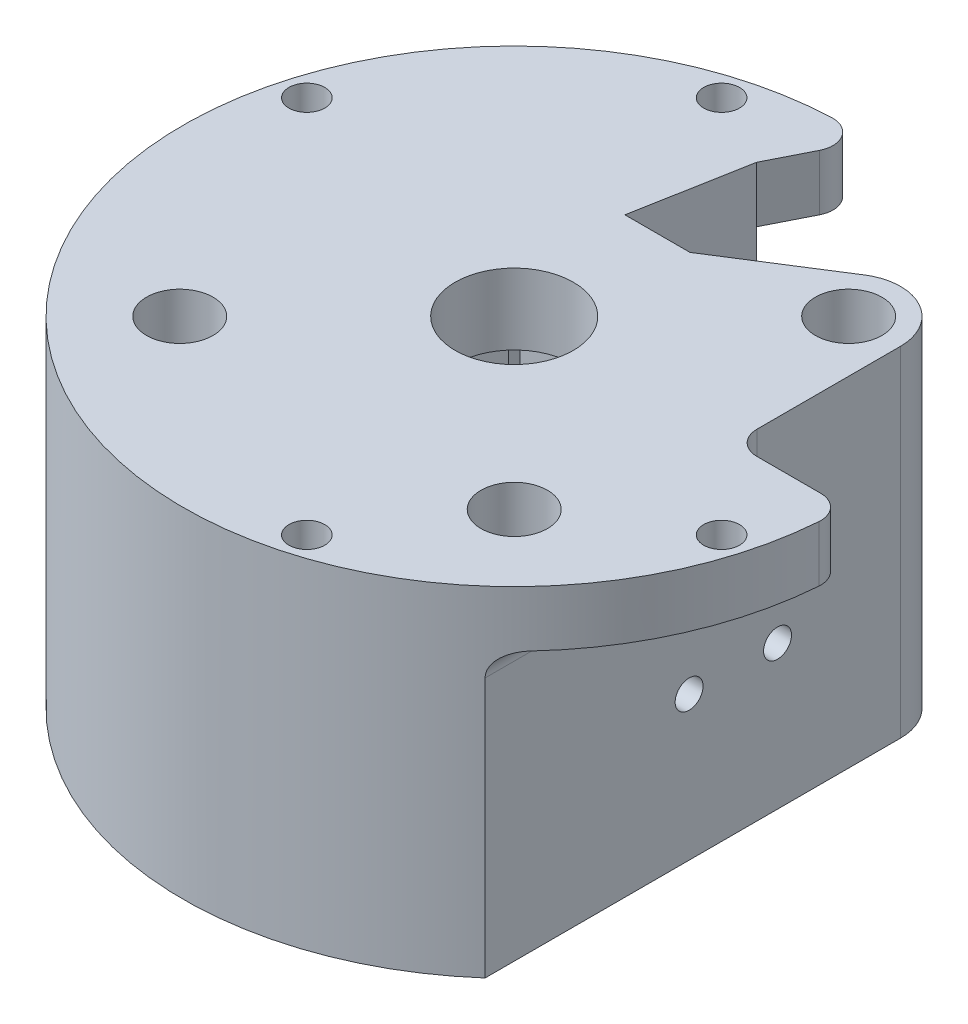
SolidWorks part; units mm, degrees
ref_plane "Front Plane" through (0, 0, 0) normal (0, 0, 1) x (1, 0, 0)
ref_plane "Top Plane" through (0, 0, 0) normal (0, 1, 0) x (1, 0, 0)
ref_plane "Right Plane" through (0, 0, 0) normal (1, 0, 0) x (0, 0, -1)
sketch "Sketch2" plane through (0, 0, 0) normal (0, 1, 0) x (1, 0, 0)
  line L0 (-46.3406, 15.0473) -> (-20.9548, -39.0545) construction
  line L1 (-17.9605, 17.9605) -> (-3.0236, 17.9605) construction
  line L2 (-17.9605, 17.9605) -> (-17.9605, -17.9605) construction
  line L3 (-17.9605, -17.9605) -> (17.9605, -17.9605) construction
  line L4 (17.9605, 17.9605) -> (17.9605, -17.9605) construction
  line L5 (-17.9605, 17.9605) -> (17.9605, -17.9605) construction
  line L6 (-17.9605, -17.9605) -> (17.9605, 17.9605) construction
  line L7 (10.05, -30.05) -> (-10.05, -30.05)
  line L8 (10.05, -30.05) -> (10.05, 10.05)
  line L9 (10.05, 10.05) -> (3.4925, 10.05)
  line L10 (-10.05, -30.05) -> (-10.05, 10.05)
  line L11 (10.05, -30.05) -> (-10.05, 10.05) construction
  line L12 (10.05, 10.05) -> (-10.05, -30.05) construction
  line L13 (-3.4925, 15.384) -> (3.4925, 15.384) construction
  line L14 (-3.4925, 15.384) -> (-3.4925, 10.05)
  line L15 (0, 10.05) -> (3.4925, 10.05) construction
  line L16 (3.4925, 15.384) -> (3.4925, 10.05)
  line L17 (0, 12.717) -> (3.4925, 10.05) construction
  line L18 (0, 12.717) -> (3.4925, 15.384) construction
  line L19 (-1.3182, 27.3309) -> (-10.8398, 32.142)
  line L20 (-1.3182, 27.3309) -> (-23.3118, -16.1961) construction
  line L21 (-23.3118, -16.1961) -> (-32.8333, -11.3851) construction
  line L22 (-10.8398, 32.142) -> (-32.8333, -11.3851) construction
  line L23 (-1.3182, 27.3309) -> (-32.8333, -11.3851) construction
  line L24 (-23.3118, -16.1961) -> (-10.8398, 32.142) construction
  line L25 (23.5324, -17.9605) -> (23.5324, -26.6597)
  line L26 (23.5324, -17.9605) -> (23.5324, 17.9605)
  line L27 (3.4925, 15.384) -> (14.9767, 22.6661)
  line L28 (-10.8398, 32.142) -> (-12.8493, 33.1573)
  line L29 (-3.4925, 15.384) -> (-1.3182, 27.3309)
  line L30 (-3.0236, 17.9605) -> (7.5558, 17.9605) construction
  line L31 (7.5558, 17.9605) -> (17.9605, 17.9605) construction
  line L32 (-3.4925, 15.384) -> (0, 12.717) construction
  line L33 (-3.4925, 10.05) -> (0, 12.717) construction
  line L34 (0, 10.05) -> (-3.4925, 10.05) construction
  line L35 (-3.4925, 10.05) -> (-10.05, 10.05)
  line L36 (-3.4925, 10.05) -> (0, 10.05) construction
  line L37 (3.4925, 10.05) -> (0, 10.05) construction
  arc A0 (-12.8493, 33.1573) -> (23.5324, -26.6597) centre (0, 0) ccw
  circle A1 centre (-17.9605, 17.9605) radius 3.5719 construction
  circle A2 centre (17.9605, 17.9605) radius 3.5719
  circle A3 centre (17.9605, -17.9605) radius 3.5719
  circle A4 centre (-17.9605, -17.9605) radius 3.5719
  arc A5 (-4.4901, 4.4901) -> (4.4901, 4.4901) centre (0, 0) ccw construction
  arc A6 (-7.1064, 7.1064) -> (7.1064, 7.1064) centre (0, 0) ccw construction
  circle A7 centre (-17.9605, -17.9605) radius 5.5719 construction
  arc A8 (23.5324, -17.9605) -> (17.9605, -12.3886) centre (17.9605, -17.9605) ccw construction
  arc A9 (23.5324, 17.9605) -> (14.9767, 22.6661) centre (17.9605, 17.9605) ccw
  arc A10 (23.5324, -26.6597) -> (-12.8493, 33.1573) centre (0, 0) ccw construction
  arc A11 (0, 10.05) -> (-7.1064, 7.1064) centre (0, 0) ccw construction
  arc A12 (4.4901, 4.4901) -> (-4.4901, 4.4901) centre (0, 0) ccw construction
  arc A13 (7.1064, 7.1064) -> (0, 10.05) centre (0, 0) ccw construction
  arc A14 (14.0206, 14.0206) -> (17.9605, 12.3886) centre (17.9605, 17.9605) ccw construction
  arc A15 (12.3886, 17.9605) -> (14.0206, 14.0206) centre (17.9605, 17.9605) ccw construction
  arc A16 (14.9767, 22.6661) -> (12.3886, 17.9605) centre (17.9605, 17.9605) ccw construction
  arc A17 (17.9605, 12.3886) -> (23.5324, 17.9605) centre (17.9605, 17.9605) ccw construction
  arc A18 (12.3886, -17.9605) -> (23.5324, -17.9605) centre (17.9605, -17.9605) ccw construction
  arc A19 (14.0206, -14.0206) -> (12.3886, -17.9605) centre (17.9605, -17.9605) ccw construction
  arc A20 (17.9605, -12.3886) -> (14.0206, -14.0206) centre (17.9605, -17.9605) ccw construction
  point P12 (0, -10)
  point P17 (0, 12.717)
  point P23 (-17.0758, 7.9729)
  point P35 (-32.1922, -15.1054)
  dimension "D1" = 71.12
  dimension "D3" = 7.1437
  dimension "D4" = 12.7
  dimension "D2" = 50.8
  dimension "D5" = 20.1
  dimension "D6" = 40.1
  dimension "D7" = 10
  dimension "D8" = 6.985
  dimension "D9" = 5.334
  dimension "D10" = 10.668
  dimension "D11" = 48.768
  dimension "D12" = 10.668
  dimension "D13" = 2
  dimension "D14" = 1
  dimension "D15" = 38.056
extrude "Boss-Extrude1" add sketch "Sketch2" along normal blind 1.905
sketch "Sketch3" plane through (0, 1.905, 0) normal (0, 1, 0) x (1, 0, 0)
  line L0 (-1.3182, 27.3309) -> (-23.3118, -16.1961) construction
  line L1 (-10.8398, 32.142) -> (-32.8333, -11.3851) construction
  line L2 (-23.3118, -16.1961) -> (-32.8333, -11.3851) construction
  line L3 (-10.8398, 32.142) -> (-32.8333, -11.3851)
  line L4 (-1.3182, 27.3309) -> (-9.7636, 10.6168)
  line L5 (-23.3118, -16.1961) -> (-32.8333, -11.3851)
  line L6 (-10.05, 10.05) -> (-9.415, 10.05) construction
  line L7 (-9.7636, 10.6168) -> (-10.05, 10.05) construction
  line L8 (-10.3364, 9.4832) -> (-23.3118, -16.1961)
  line L9 (-10.05, 10.05) -> (-10.3364, 9.4832) construction
  line L10 (-10.05, 9.415) -> (-10.05, 10.05) construction
  line L11 (-10.05, 10.05) -> (-3.4925, 10.05)
  line L12 (-3.4925, 10.05) -> (-3.4925, 15.384)
  line L13 (-3.4925, 15.384) -> (-1.3182, 27.3309)
  line L14 (-1.3182, 27.3309) -> (-12.8493, 33.1573)
  line L15 (23.5324, -26.6597) -> (23.5324, 17.9605)
  line L16 (14.9767, 22.6661) -> (3.4925, 15.384)
  line L17 (3.4925, 15.384) -> (3.4925, 10.05)
  line L18 (3.4925, 10.05) -> (10.05, 10.05)
  line L19 (10.05, 10.05) -> (10.05, -30.05)
  line L20 (10.05, -30.05) -> (-10.05, -30.05)
  line L21 (-10.05, -30.05) -> (-10.05, 10.05)
  line L22 (-9.415, 10.05) -> (-3.4925, 10.05)
  line L23 (-3.4925, 10.05) -> (-3.4925, 15.384)
  line L24 (-3.4925, 15.384) -> (-1.3182, 27.3309)
  line L25 (-10.8398, 32.142) -> (-12.8493, 33.1573)
  line L26 (23.5324, -26.6597) -> (23.5324, 17.9605)
  line L27 (14.9767, 22.6661) -> (3.4925, 15.384)
  line L28 (3.4925, 15.384) -> (3.4925, 10.05)
  line L29 (3.4925, 10.05) -> (10.05, 10.05)
  line L30 (10.05, 10.05) -> (10.05, -30.05)
  line L31 (10.05, -30.05) -> (-10.05, -30.05)
  line L32 (-10.05, -30.05) -> (-10.05, 9.415)
  line L33 (-1.3182, 27.3309) -> (-10.8398, 32.142) construction
  arc A0 (-10.3364, 9.4832) -> (-10.05, 9.415) centre (-10.05, 10.05) ccw
  circle A1 centre (17.9605, 17.9605) radius 3.5719 construction
  circle A2 centre (17.9605, -17.9605) radius 3.5719 construction
  arc A3 (-12.8493, 33.1573) -> (23.5324, -26.6597) centre (0, 0) ccw
  arc A4 (23.5324, 17.9605) -> (14.9767, 22.6661) centre (17.9605, 17.9605) ccw
  arc A5 (-12.8493, 33.1573) -> (23.5324, -26.6597) centre (0, 0) ccw
  arc A6 (23.5324, 17.9605) -> (14.9767, 22.6661) centre (17.9605, 17.9605) ccw
  circle A7 centre (-17.9605, -17.9605) radius 3.5719 construction
  circle A8 centre (17.9605, 17.9605) radius 3.5719
  circle A9 centre (17.9605, -17.9605) radius 3.5719
  circle A10 centre (-17.9605, -17.9605) radius 3.5719
  arc A11 (-9.7636, 10.6168) -> (-10.3364, 9.4832) centre (-10.05, 10.05) ccw construction
  arc A12 (-10.05, 9.415) -> (-9.415, 10.05) centre (-10.05, 10.05) ccw construction
  arc A13 (-9.415, 10.05) -> (-9.7636, 10.6168) centre (-10.05, 10.05) ccw
  dimension "D1" = 1.27
  dimension "D2" = 0
extrude "Boss-Extrude2" add sketch "Sketch3" along normal blind 19.558
sketch "Sketch4" plane through (0, 21.463, 0) normal (0, 1, 0) x (1, 0, 0)
  line L0 (0, 10.05) -> (3.4925, 10.05) construction
  line L1 (-3.4925, 15.384) -> (3.4925, 15.384) construction
  line L2 (0, 10.05) -> (-3.4925, 10.05) construction
  line L3 (0, 10.05) -> (-3.4925, 10.05)
  line L4 (0, 10.05) -> (3.4925, 10.05)
  line L5 (-3.4925, 15.384) -> (3.4925, 15.384)
  line L6 (-23.3118, -16.1961) -> (-32.8333, -11.3851) construction
  line L7 (-10.8398, 32.142) -> (-32.8333, -11.3851) construction
  line L8 (-1.3182, 27.3309) -> (-23.3118, -16.1961) construction
  line L9 (-23.3118, -16.1961) -> (-32.8333, -11.3851)
  line L10 (-10.8398, 32.142) -> (-32.8333, -11.3851)
  line L11 (-10.05, 10.05) -> (-3.4925, 10.05)
  line L12 (-10.05, -30.05) -> (-10.05, 10.05)
  line L13 (10.05, -30.05) -> (-10.05, -30.05)
  line L14 (10.05, 10.05) -> (10.05, -30.05)
  line L15 (3.4925, 10.05) -> (10.05, 10.05)
  line L16 (3.4925, 15.384) -> (3.4925, 10.05)
  line L17 (14.9767, 22.6661) -> (3.4925, 15.384)
  line L18 (23.5324, -26.6597) -> (23.5324, 17.9605)
  line L19 (-1.3182, 27.3309) -> (-12.8493, 33.1573)
  line L20 (-3.4925, 15.384) -> (-1.3182, 27.3309)
  line L21 (-3.4925, 10.05) -> (-3.4925, 15.384)
  line L22 (-9.415, 10.05) -> (-3.4925, 10.05)
  line L23 (-10.05, -30.05) -> (-10.05, 9.415)
  line L24 (10.05, -30.05) -> (-10.05, -30.05)
  line L25 (10.05, 10.05) -> (10.05, -30.05)
  line L26 (3.4925, 10.05) -> (10.05, 10.05)
  line L27 (3.4925, 15.384) -> (3.4925, 10.05) construction
  line L28 (14.9767, 22.6661) -> (3.4925, 15.384)
  line L29 (23.5324, -26.6597) -> (23.5324, 17.9605)
  line L30 (-10.8398, 32.142) -> (-12.8493, 33.1573)
  line L31 (-3.4925, 15.384) -> (-1.3182, 27.3309)
  line L32 (-3.4925, 10.05) -> (-3.4925, 15.384) construction
  line L33 (-1.3182, 27.3309) -> (-9.7636, 10.6168)
  line L34 (-1.3182, 27.3309) -> (-10.8398, 32.142) construction
  line L35 (-10.05, 10.05) -> (-10.3364, 9.4832) construction
  line L36 (-10.3364, 9.4832) -> (-23.3118, -16.1961)
  line L37 (-10.05, 9.415) -> (-10.05, 10.05) construction
  line L38 (-10.05, 10.05) -> (-9.415, 10.05) construction
  line L39 (-9.7636, 10.6168) -> (-10.05, 10.05) construction
  circle A0 centre (17.9605, 17.9605) radius 3.5719 construction
  circle A1 centre (17.9605, -17.9605) radius 3.5719 construction
  arc A2 (23.5324, 17.9605) -> (14.9767, 22.6661) centre (17.9605, 17.9605) ccw
  arc A3 (-12.8493, 33.1573) -> (23.5324, -26.6597) centre (0, 0) ccw
  arc A4 (23.5324, 17.9605) -> (14.9767, 22.6661) centre (17.9605, 17.9605) ccw
  arc A5 (-12.8493, 33.1573) -> (23.5324, -26.6597) centre (0, 0) ccw
  circle A6 centre (-17.9605, -17.9605) radius 3.5719 construction
  circle A7 centre (17.9605, 17.9605) radius 3.5719
  circle A8 centre (17.9605, -17.9605) radius 3.5719
  circle A9 centre (-17.9605, -17.9605) radius 3.5719
  arc A10 (-9.415, 10.05) -> (-9.7636, 10.6168) centre (-10.05, 10.05) ccw construction
  arc A11 (-10.3364, 9.4832) -> (-10.05, 9.415) centre (-10.05, 10.05) ccw construction
  arc A12 (-9.415, 10.05) -> (-9.7636, 10.6168) centre (-10.05, 10.05) ccw
  arc A13 (-10.3364, 9.4832) -> (-10.05, 9.415) centre (-10.05, 10.05) ccw
  dimension "D1" = 0
extrude "Boss-Extrude3" add sketch "Sketch4" along normal blind 7.366
sketch "Sketch5" plane through (0, 28.829, 0) normal (0, 1, 0) x (1, 0, 0)
  line L0 (3.4925, 15.384) -> (-3.4925, 15.384) construction
  line L1 (3.4925, 15.384) -> (-3.4925, 15.384)
  line L11 (-10.05, 10.05) -> (-3.4925, 10.05)
  line L12 (-10.05, -30.05) -> (-10.05, 10.05)
  line L13 (10.05, -30.05) -> (-10.05, -30.05)
  line L14 (10.05, 10.05) -> (10.05, -30.05)
  line L15 (3.4925, 10.05) -> (10.05, 10.05)
  line L16 (3.4925, 15.384) -> (3.4925, 10.05)
  line L17 (14.9767, 22.6661) -> (3.4925, 15.384)
  line L18 (23.5324, -26.6597) -> (23.5324, 17.9605)
  line L19 (-1.3182, 27.3309) -> (-12.8493, 33.1573)
  line L20 (-3.4925, 15.384) -> (-1.3182, 27.3309)
  line L21 (-3.4925, 10.05) -> (-3.4925, 15.384)
  line L22 (-10.05, 10.05) -> (-3.4925, 10.05) construction
  line L23 (-10.05, -30.05) -> (-10.05, 10.05) construction
  line L24 (10.05, -30.05) -> (-10.05, -30.05) construction
  line L25 (10.05, 10.05) -> (10.05, -30.05) construction
  line L26 (3.4925, 10.05) -> (10.05, 10.05) construction
  line L27 (3.4925, 15.384) -> (3.4925, 10.05) construction
  line L28 (14.9767, 22.6661) -> (3.4925, 15.384)
  line L29 (23.5324, -26.6597) -> (23.5324, 17.9605)
  line L30 (-1.3182, 27.3309) -> (-12.8493, 33.1573)
  line L31 (-3.4925, 15.384) -> (-1.3182, 27.3309)
  line L32 (-3.4925, 10.05) -> (-3.4925, 15.384) construction
  circle A0 centre (17.9605, 17.9605) radius 3.5719 construction
  circle A1 centre (17.9605, -17.9605) radius 3.5719 construction
  arc A2 (23.5324, 17.9605) -> (14.9767, 22.6661) centre (17.9605, 17.9605) ccw
  arc A3 (-12.8493, 33.1573) -> (23.5324, -26.6597) centre (0, 0) ccw
  arc A4 (23.5324, 17.9605) -> (14.9767, 22.6661) centre (17.9605, 17.9605) ccw
  arc A5 (-12.8493, 33.1573) -> (23.5324, -26.6597) centre (0, 0) ccw
  circle A6 centre (-17.9605, -17.9605) radius 3.5719 construction
  circle A7 centre (17.9605, 17.9605) radius 3.5719
  circle A8 centre (17.9605, -17.9605) radius 3.5719
  circle A9 centre (-17.9605, -17.9605) radius 3.5719
  arc A10 (4.4901, 4.4901) -> (-4.4901, 4.4901) centre (0, 0) ccw construction
  arc A11 (-4.4901, 4.4901) -> (4.4901, 4.4901) centre (0, 0) ccw construction
  arc A12 (4.4901, 4.4901) -> (-4.4901, 4.4901) centre (0, 0) ccw
  arc A13 (-4.4901, 4.4901) -> (4.4901, 4.4901) centre (0, 0) ccw
  dimension "D1" = 0
extrude "Boss-Extrude4" add sketch "Sketch5" along normal blind 7.62
sketch "Sketch8" plane through (0, 36.449, 0) normal (0, 1, 0) x (1, 0, 0)
  line L0 (-1.3182, 27.3309) -> (-12.8493, 33.1573)
  line L1 (-1.3182, 27.3309) -> (2.7846, 35.4508)
  line L2 (23.5324, 0) -> (35.56, 0)
  line L3 (23.5324, -17.9605) -> (23.5324, 17.9605) construction
  line L4 (23.5324, -17.9605) -> (23.5324, 0)
  line L5 (23.5324, -17.9605) -> (23.5324, -26.6597) construction
  line L6 (23.5324, -17.9605) -> (23.5324, -26.6597)
  arc A0 (23.5324, -26.6597) -> (-12.8493, 33.1573) centre (0, 0) ccw construction
  arc A1 (23.5324, -26.6597) -> (35.56, 0) centre (0, 0) ccw
  arc A2 (35.56, 0) -> (2.7846, 35.4508) centre (0, 0) ccw construction
  arc A3 (2.7846, 35.4508) -> (-12.8493, 33.1573) centre (0, 0) ccw
extrude "Boss-Extrude5" add sketch "Sketch8" against normal blind 6
sketch "Sketch7" plane through (0, 36.449, 0) normal (0, 1, 0) x (1, 0, 0)
  line L0 (-31.4663, 9.1924) -> (-9.1924, 31.4663) construction
  line L1 (-9.1924, 31.4663) -> (31.4663, -9.1924) construction
  line L2 (31.4663, -9.1924) -> (9.1924, -31.4663) construction
  line L3 (9.1924, -31.4663) -> (-31.4663, 9.1924) construction
  line L4 (-17.9605, -17.9605) -> (17.9605, 17.9605) construction
  line L5 (-31.4663, 9.1924) -> (31.4663, -9.1924) construction
  line L6 (9.1924, -31.4663) -> (-9.1924, 31.4663) construction
  circle A0 centre (-31.4663, 9.1924) radius 1.925
  circle A1 centre (-9.1924, 31.4663) radius 1.925
  circle A2 centre (31.4663, -9.1924) radius 1.925
  circle A3 centre (9.1924, -31.4663) radius 1.925
  point P6 (0, 0)
  dimension "D3" = 3.85
  dimension "D1" = 57.5
  dimension "D2" = 31.5
extrude "Cut-Extrude2" cut sketch "Sketch7" against normal blind 5.75
sketch "Sketch6" plane through (23.5324, 0, 0) normal (1, 0, 0) x (0, 0, -1)
  line L1 (-4.75, 15.449) -> (4.75, 15.449) construction
  line L5 (0, 30.449) -> (-26.6597, 30.449) construction
  line L6 (0, 30.449) -> (-26.6597, 30.449) construction
  circle A0 centre (-4.75, 15.449) radius 1.5
  circle A1 centre (4.75, 15.449) radius 1.5
  point P3 (0, 15.449)
  dimension "D3" = 15
  dimension "D1" = 3
  dimension "D2" = 9.5
fillet "Fillet1" radius 2.54 8 edges at (23.5324, 30.449, 13.3299) (0, 21.463, -10.05) (0, 21.463, -15.384) (2.7846, 33.449, -35.4508) (-12.8493, 15.2245, -33.1573) (3.4925, 0, -12.717) (35.56, 33.449, 0) (23.5324, 33.449, 0)
extrude "Cut-Extrude3" cut sketch "Sketch6" against normal blind 4
equation "\"AIRFRAME_OD\"= 3.091in"
equation "\"AIRFRAME_ID\"= 3.00in"
equation "\"FLAT_T\"= 0.125in"
equation "\"NOSE_EXP_L\"= 3.5in"
equation "\"NOSE_SHOULDER_L\"= 5in"
equation "\"MAIN_L\"= 30in"
equation "\"RECO_COUP_L\"= 6in"
equation "\"RECO_SWITCH_L\"= 1.5in"
equation "\"DROGUE_L\"= 14in"
equation "\"ATS_FORE_COUP_L\"= 4in"
equation "\"ATS_AFT_COUP_L\"= 2.5in"
equation "\"LOWER_L\"= 16in"
equation "\"FIN_N\"= 4"
equation "\"CR_AFT_X\"= 0.5in"
equation "\"CR_FORE_X\"= 6in"
equation "\"COUPLER_OD\"= 2.998in"
equation "\"COUPLER_ID\"= 2.875in"
equation "\"RECO_ROD_X\"= 1.5in"
equation "\"ATS_ROD_X\"= 2in"
equation "\"FIN_ROOT\"= 5in"
equation "\"FIN_X\"= 0.75in"
equation "\"MOTOR_OD\"= 2.25in"
equation "\"MOTOR_ID\"= 2.126in"
equation "\"MOTOR_L\"= 8in"
equation "\"MOTOR_LOWER_X\"= 0.5in"
equation "\"NOSE_CONE_L\"=14.5in"
equation "\"ATS_LIPO_L\"= 1.92in"
equation "\"ATS_LIPO_W\"= 0.42in"
equation "\"ATS_LIPO_H\"= 0.94in "
equation "\"ATS_STANDOFF_H\"= 10mm"
equation "\"ATS_STANDOFF_OD\"= 5.2mm"
equation "\"ATS_PCB_L\"= 2.5in"
equation "\"ATS_PCB_W\"= 1.45in"
equation "\"ATS_PCB_H\"= 1.2in"
equation "\"ATS_PCB_HOLESEP_W\"= 1.33in - 0.0985in"
equation "\"ATS_ALTI_L\"= 1.05in"
equation "\"ATS_ALTI_W\"= 0.7in"
equation "\"ATS_ALTI_H\"= 0.4in"
equation "\"D11@Sketch2\"=\"ATS_LIPO_L\""
equation "\"D12@Sketch2\"=\"ATS_LIPO_W\""
equation "\"D1@Boss-Extrude2\"=\"ATS_LIPO_H\""
